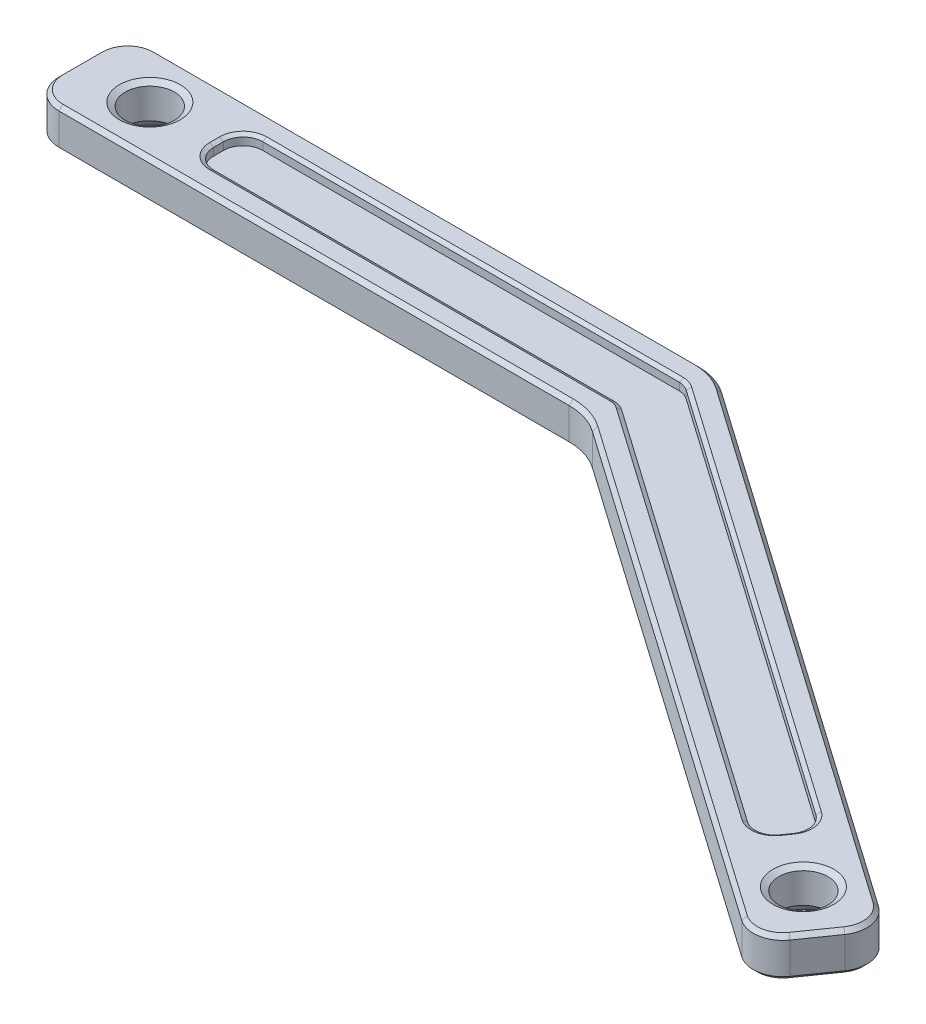
SolidWorks part; units mm, degrees
ref_plane "前视基准面" through (0, 0, 0) normal (0, 0, 1) x (1, 0, 0)
ref_plane "上视基准面" through (0, 0, 0) normal (0, 1, 0) x (1, 0, 0)
ref_plane "右视基准面" through (0, 0, 0) normal (1, 0, 0) x (0, 0, -1)
other "Configuration Table"
sketch "草图1" plane through (0, 0, 0) normal (0, 1, 0) x (1, 0, 0)
  line L0 (-28.6729, 11.4451) -> (1.3271, 11.4451)
  line L1 (1.3271, 11.4451) -> (29.9974, -8.6301)
  line L2 (29.9974, -8.6301) -> (27.1295, -12.7259)
  line L3 (27.1295, -12.7259) -> (-0.2494, 6.4451)
  line L4 (-0.2494, 6.4451) -> (-28.6729, 6.4451)
  line L5 (-28.6729, 6.4451) -> (-28.6729, 11.4451)
  line L6 (28.5635, -10.678) -> (-3.0315, 11.4451) construction
  line L7 (-28.6729, 8.9451) -> (4.8975, 8.9451) construction
  circle A0 centre (26.1825, -9.0108) radius 1.25
  circle A1 centre (-25.0486, 8.9451) radius 1.25
  dimension "D5" = 2.5
  dimension "D6" = 2.5
  dimension "D1" = 5
  dimension "D2" = 30
  dimension "D3" = 35
  dimension "D4" = 5
  dimension "D7" = 145
extrude "凸台-拉伸1" add sketch "草图1" along normal blind 2
fillet "圆角1" radius 1.5 4 edges at (-28.6729, 1, -11.4451) (-28.6729, 1, -6.4451) (29.9974, 1, 8.6301) (27.1295, 1, 12.7259)
fillet "圆角2" radius 3 1 edges at (1.3271, 1, -11.4451)
fillet "圆角3" radius 3 1 edges at (-0.2494, 1, -6.4451)
sketch "草图2" plane through (0, 0, 0) normal (0, -1, 0) x (1, 0, 0)
  line L0 (-20.5486, -7.6951) -> (-0.1706, -7.6951)
  line L1 (0.403, -7.5142) -> (21.7793, 7.4536)
  line L2 (23.1721, 7.2081) -> (23.4589, 6.7985)
  line L3 (23.2133, 5.4058) -> (1.1912, -10.0142)
  line L4 (0.6177, -10.1951) -> (-20.5486, -10.1951)
  line L5 (-21.5486, -9.1951) -> (-21.5486, -8.6951)
  line L6 (-27.1729, -6.4451) -> (-1.1953, -6.4451) construction
  line L7 (0.3812, -11.4451) -> (-27.1729, -11.4451) construction
  line L9 (0.5254, -5.9025) -> (25.9008, 11.8655) construction
  line L10 (28.7687, 7.7697) -> (2.1019, -10.9025) construction
  line L11 (0.1447, -7.6951) -> (0.933, -10.1951) construction
  arc A0 (-0.1706, -7.6951) -> (0.403, -7.5142) centre (-0.1706, -6.6951) ccw
  arc A1 (1.1912, -10.0142) -> (0.6177, -10.1951) centre (0.6177, -9.1951) cw
  arc A2 (-20.5486, -10.1951) -> (-21.5486, -9.1951) centre (-20.5486, -9.1951) cw
  arc A3 (-20.5486, -7.6951) -> (-21.5486, -8.6951) centre (-20.5486, -8.6951) ccw
  arc A4 (23.4589, 6.7985) -> (23.2133, 5.4058) centre (22.6397, 6.2249) cw
  arc A5 (21.7793, 7.4536) -> (23.1721, 7.2081) centre (22.3529, 6.6345) cw
  circle A6 centre (-25.0486, -8.9451) radius 1.25 construction
  circle A7 centre (26.1825, 9.0108) radius 1.25 construction
  dimension "D5" = 1
  dimension "D1" = 1.25
  dimension "D2" = 1.25
  dimension "D3" = 1.25
  dimension "D4" = 1.25
  dimension "D6" = 3.5
  dimension "D7" = 3.5
sketch "草图5" plane through (0, 2, 0) normal (0, 1, 0) x (1, 0, 0)
  line L0 (-20.5486, 10.1951) -> (0.6764, 10.1951)
  line L1 (1.1885, 10.0161) -> (23.2133, -5.4058)
  line L3 (23.4589, -6.7985) -> (23.1721, -7.2081)
  line L5 (21.7793, -7.4536) -> (0.403, 7.5142)
  line L9 (-21.5486, 8.6951) -> (-21.5486, 9.1951)
  line L13 (-21.5486, 9.1951) -> (-21.5486, 8.6951) construction
  line L15 (0.403, 7.5142) -> (21.7793, -7.4536) construction
  line L17 (-20.5486, 7.6951) -> (-0.1706, 7.6951)
  line L18 (0.3812, 11.4451) -> (-27.1729, 11.4451) construction
  line L19 (0.3812, 11.4451) -> (-27.1729, 11.4451) construction
  line L21 (28.7687, -7.7697) -> (2.1019, 10.9025) construction
  arc A0 (23.4589, -6.7985) -> (23.2133, -5.4058) centre (22.6397, -6.2249) ccw construction
  arc A1 (-21.5486, 9.1951) -> (-20.5486, 10.1951) centre (-20.5486, 9.1951) cw
  arc A2 (-20.5486, 10.1951) -> (-21.5486, 9.1951) centre (-20.5486, 9.1951) ccw construction
  arc A3 (-21.5486, 8.6951) -> (-20.5486, 7.6951) centre (-20.5486, 8.6951) ccw
  arc A4 (-21.5486, 8.6951) -> (-20.5486, 7.6951) centre (-20.5486, 8.6951) ccw construction
  arc A5 (-0.1706, 7.6951) -> (0.403, 7.5142) centre (-0.1706, 6.6951) cw
  arc A6 (0.6764, 10.1951) -> (1.1885, 10.0161) centre (0.615, 9.197) cw
  arc A7 (21.7793, -7.4536) -> (23.1721, -7.2081) centre (22.3529, -6.6345) ccw
  arc A8 (21.7793, -7.4536) -> (23.1721, -7.2081) centre (22.3529, -6.6345) ccw construction
  arc A9 (23.2133, -5.4058) -> (23.4589, -6.7985) centre (22.6397, -6.2249) cw
  point P3 (-6.81, 7.3272)
  point P12 (9.3842, 4.2784)
  point P21 (8.268, 10.1951)
  point P28 (0.7678, 10.1951)
  point P29 (2.2703, 10.0006)
  point P53 (0.6764, 10.1951)
  point P54 (1.1885, 10.0161)
  dimension "D1" = 1
  dimension "D2" = 1.25
extrude "切除-拉伸1" cut sketch "草图2" against normal blind 0.5
extrude "切除-拉伸2" cut sketch "草图5" against normal blind 0.5
chamfer "倒角2" distance 0.2 angle 30 24 edges at (11.0912, 0, -0.0303) (0.1301, 0, -7.6488) (22.5266, 0, 7.6193) (-10.3596, 0, -7.6951) (23.3155, 0, 7.0033) (-21.2557, 0, -7.988) (23.6245, 0, 6.0513) (-21.5486, 0, -8.9451) (12.2023, 0, -2.3042) (-21.2557, 0, -9.9022) (0.9184, 0, -10.1488) (-9.9655, 0, -10.1951) (11.0912, 2, -0.0303) (22.5266, 2, 7.6193) (0.1301, 2, -7.6488) (23.3155, 2, 7.0033) (-10.3596, 2, -7.6951) (23.6245, 2, 6.0513) (-21.2557, 2, -7.988) (12.2009, 2, -2.3052) (-21.5486, 2, -8.9451) (0.9449, 2, -10.141) (-21.2557, 2, -9.9022) (-9.9361, 2, -10.1951)
chamfer "倒角3" distance 0.2 angle 45 24 edges at (13.2131, 0, 2.9815) (27.0216, 0, 12.114) (-0.2932, 0, -6.3062) (28.5635, 0, 10.678) (-14.1841, 0, -6.4451) (29.3855, 0, 8.738) (-28.2336, 0, -6.8844) (15.4353, 0, -1.5664) (-28.6729, 0, -8.9451) (1.2833, 0, -11.3062) (-28.2336, 0, -11.0057) (-13.3959, 0, -11.4451) (13.2131, 2, 2.9815) (27.0216, 2, 12.114) (-0.2932, 2, -6.3062) (28.5635, 2, 10.678) (-14.1841, 2, -6.4451) (29.3855, 2, 8.738) (-28.2336, 2, -6.8844) (15.4353, 2, -1.5664) (-28.6729, 2, -8.9451) (1.2833, 2, -11.3062) (-28.2336, 2, -11.0057) (-13.3959, 2, -11.4451)
chamfer "倒角4" distance 0.3 angle 30 4 edges at (-25.0486, 2, -7.6951) (26.1825, 2, 10.2608) (-25.0486, 0, -7.6951) (26.1825, 0, 10.2608)
